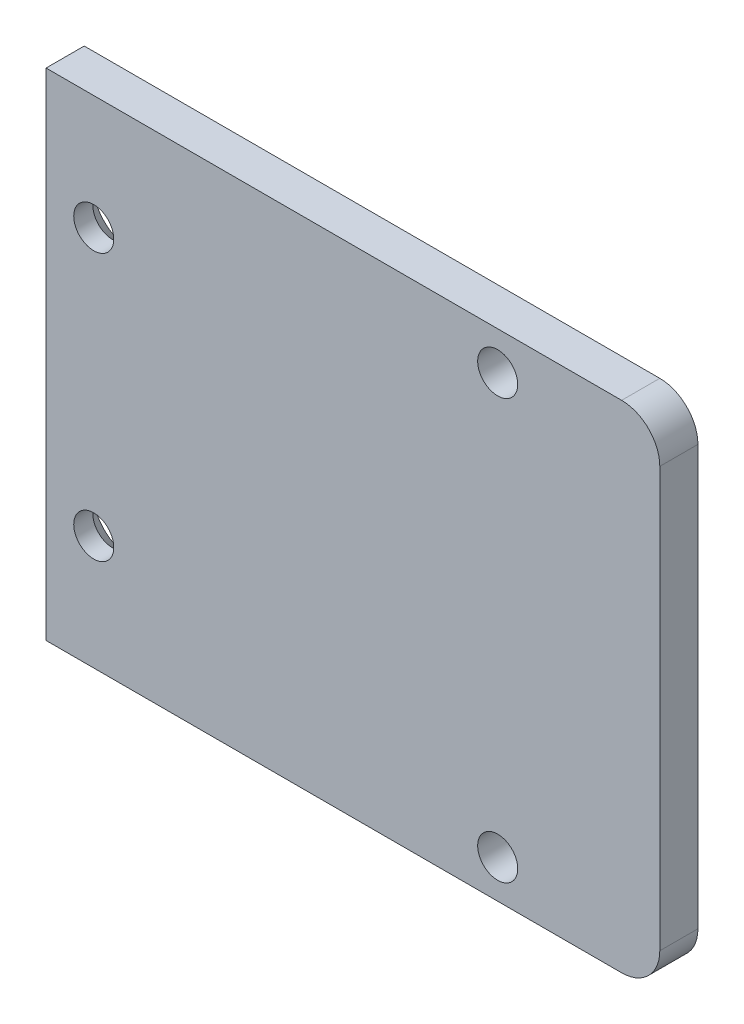
SolidWorks part; units mm, degrees
ref_plane "前视基准面" through (0, 0, 0) normal (0, 0, 1) x (1, 0, 0)
ref_plane "上视基准面" through (0, 0, 0) normal (0, 1, 0) x (1, 0, 0)
ref_plane "右视基准面" through (0, 0, 0) normal (1, 0, 0) x (0, 0, -1)
other "Configuration Table"
sketch "草图2" plane through (0, 0, 0) normal (0, 0, 1) x (1, 0, 0)
  line L0 (-40.9928, -32.4342) -> (-15.4928, -32.4342) construction
  line L1 (15.1907, -6.4342) -> (-16.9928, -6.4342)
  line L2 (15.1907, -6.4342) -> (15.1907, -32.4342)
  line L3 (15.1907, -32.4342) -> (-16.9928, -32.4342)
  line L4 (-16.9928, -6.4342) -> (-16.9928, -32.4342)
  line L5 (-16.9928, 27.5658) -> (-16.9928, -34.4342) construction
  line L6 (13.1907, -6.4342) -> (-12.8093, -6.4342) construction
  point P8 (15.7609, 1.2052)
  point P11 (15.1907, -23.2068)
extrude "凸台-拉伸1" add sketch "草图2" along normal blind 2
fillet "圆角1" radius 2 2 edges at (15.1907, -32.4342, 1) (15.1907, -6.4342, 1)
sketch "草图3" plane through (0, 0, 2) normal (0, 0, 1) x (1, 0, 0)
  circle A0 centre (6.6907, -8.4342) radius 1.05
  circle A1 centre (6.6907, -30.4342) radius 1.05
  dimension "D1" = 2.1
extrude "切除-拉伸1" cut sketch "草图3" against normal up to next
sketch "草图4" plane through (0, 0, 0) normal (0, 0, -1) x (-1, 0, 0)
  line L0 (-13.1907, -6.4342) -> (16.9928, -6.4342) construction
  line L2 (16.9928, -34.4342) -> (16.9928, 27.5658) construction
  line L4 (16.9928, -32.4342) -> (-13.1907, -32.4342) construction
  circle A0 centre (14.4928, -12.4342) radius 1.05
  circle A1 centre (14.4928, -26.4342) radius 1.05
  point P10 (0, 0)
  dimension "D1" = 2.1
  dimension "D2" = 6
  dimension "D3" = 6
  dimension "D4" = 2.5
extrude "切除-拉伸2" cut sketch "草图4" against normal up to next
chamfer "倒角1" distance 1 angle 45 2 edges at (-15.5428, -12.4342, 0) (-15.5428, -26.4342, 0)
